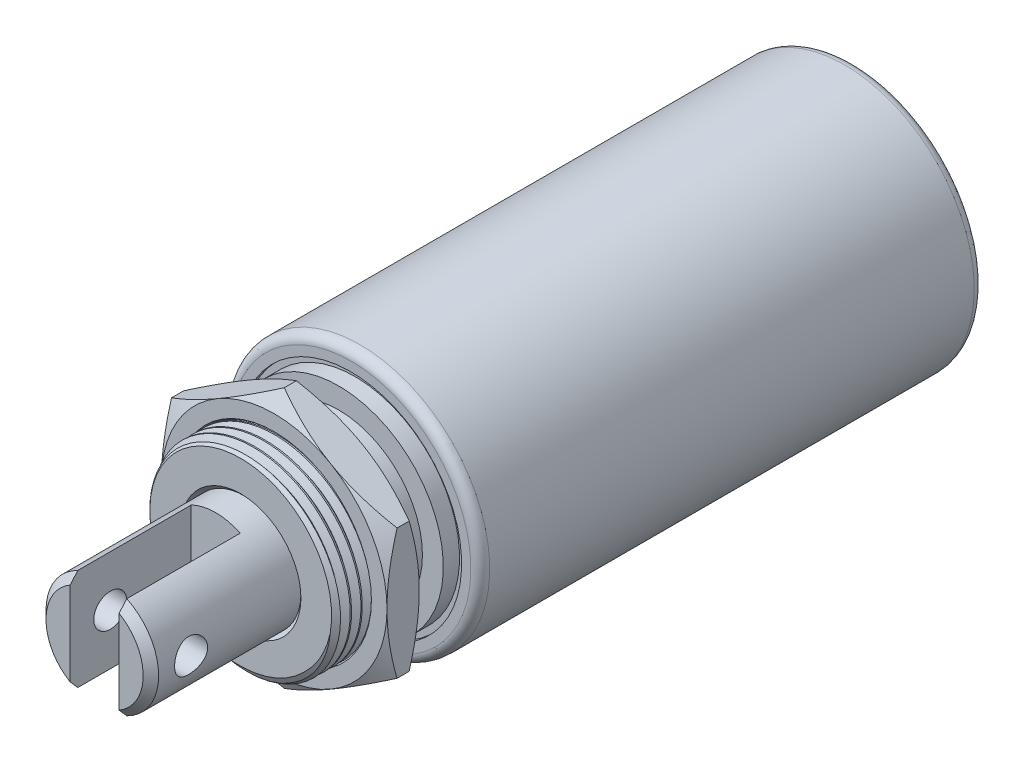
SolidWorks part; units mm, degrees
ref_plane "Front Plane" through (0, 0, 0) normal (0, 0, 1) x (1, 0, 0)
ref_plane "Top Plane" through (0, 0, 0) normal (0, 1, 0) x (1, 0, 0)
ref_plane "Right Plane" through (0, 0, 0) normal (1, 0, 0) x (0, 0, -1)
sketch "Sketch0" plane through (0, 0, 0) normal (1, 0, 0) x (0, 0, -1)
  line L0 (0, 0) -> (51.1556, 0) construction
  line L1 (0, 0) -> (-24.0538, 0) construction
  line L2 (51.1556, 12.7635) -> (51.1556, -12.7635) construction
  line L3 (0, 9.464) -> (0, -9.464) construction
  line L4 (-24.0538, 5.5499) -> (-24.0538, -5.5499) construction
  line L5 (-24.0538, 0) -> (-49.4538, 0) construction
  point P10 (-20.0914, 0)
  point P12 (-9.652, 0)
  dimension "D1" = 20.0914
  dimension "Lg." = 51.1556
  dimension "Dia." = 25.527
  dimension "Rod Dia." = 11.0998
  dimension "A" = 24.0538
  dimension "Thread OD" = 18.9281
  dimension "Stroke" = 25.4
  dimension "D2" = 3.9624
  dimension "D3" = 9.652
sketch "Sketch1" plane through (0, 0, 0) normal (1, 0, 0) x (0, 0, -1)
  line L0 (51.1556, 0) -> (0, 0) construction
  line L1 (49.8729, 12.7635) -> (2.1209, 12.7635)
  line L2 (51.1556, 2.2225) -> (51.1556, 0)
  line L3 (51.1556, 0) -> (0, 0)
  line L4 (1.6002, 10.922) -> (1.6002, 10.3124)
  line L5 (50.8, 2.5781) -> (50.8, 11.8364)
  line L6 (1.1938, 11.8364) -> (1.1938, 10.922)
  line L7 (1.1938, 10.922) -> (1.6002, 10.922)
  line L8 (1.6002, 10.3124) -> (0, 10.3124)
  line L9 (0, 10.3124) -> (0, 0)
  arc A0 (51.1556, 2.2225) -> (50.8, 2.5781) centre (50.8, 2.2225) ccw
  arc A1 (50.8, 11.8364) -> (49.8729, 12.7635) centre (49.8729, 11.8364) ccw
  arc A2 (1.1938, 11.8364) -> (2.1209, 12.7635) centre (2.1209, 11.8364) cw
  dimension "D1" = 0.9271
  dimension "D4" = 1.1938
  dimension "D2" = 0.3556
  dimension "D3" = 4.445
  dimension "D5" = 21.844
  dimension "D6" = 0.4064
  dimension "D7" = 20.6248
revolve "Revolve1" add sketch "Sketch1" angle 360 mid plane about L0
sketch "Sketch2" plane through (0, 0, 0) normal (1, 0, 0) x (0, 0, -1)
  line L0 (0, 0) -> (-24.0538, 0) construction
  line L3 (-9.652, 5.9309) -> (-9.652, 8.956)
  line L4 (-9.652, 8.956) -> (-9.144, 9.464)
  line L5 (-9.144, 9.464) -> (-2.479, 9.464)
  line L6 (-2.479, 9.464) -> (-1.27, 8.255)
  line L7 (-1.27, 8.255) -> (0, 8.255)
  line L8 (0, 8.255) -> (0, 5.5499)
  line L9 (-9.271, 5.5499) -> (0, 5.5499)
  line L11 (-9.271, 5.5499) -> (-9.652, 5.9309)
  dimension "D1" = 1.27
  dimension "D4" = 0.508
  dimension "D5" = 9.652
  dimension "D2" = 45
  dimension "D6" = 1.209
  dimension "D3" = 45
  dimension "D8" = 0.381
  dimension "D7" = 45
revolve "Revolve2" add sketch "Sketch2" angle 360 mid plane about L0
sketch "Sketch3" plane through (0, 0, 0) normal (1, 0, 0) x (0, 0, -1)
  line L0 (-24.0538, 0) -> (0, 0) construction
  line L1 (-23.2918, 5.5499) -> (-24.0538, 4.7879)
  line L2 (0, 0) -> (-24.0538, 0)
  line L3 (0, 0) -> (0, 5.5499)
  line L4 (0, 5.5499) -> (-23.2918, 5.5499)
  line L5 (-24.0538, 0) -> (-24.0538, 4.7879)
  line L6 (-23.2918, 5.5499) -> (-24.0538, 5.5499) construction
  line L7 (-24.0538, 5.5499) -> (-24.0538, 4.7879) construction
  dimension "D1" = 0.762
revolve "Revolve3" add sketch "Sketch3" angle 360 mid plane about L2
sketch "Sketch4" plane through (0, 0, 0) normal (0, 1, 0) x (0, 0, -1)
  line L1 (-24.0538, 2.413) -> (-12.1158, 2.413)
  line L2 (-24.0538, 2.413) -> (-24.0538, -2.413)
  line L3 (-24.0538, -2.413) -> (-12.1158, -2.413)
  line L4 (-12.1158, 2.413) -> (-12.1158, -2.413)
  dimension "D1" = 4.826
  dimension "D2" = 11.938
extrude "Cut-Extrude1" cut sketch "Sketch4" against normal up to surface and the other way up to surface up to face at (0, 5.5499, 23.2918) other way up to face at (0, 5.5499, 23.2918)
sketch "Sketch5" plane through (0, 0, 0) normal (1, 0, 0) x (0, -1, 0)
  line L0 (0, -24.0538) -> (0, -20.0914) construction
  circle A0 centre (0, -20.0914) radius 1.6256
  dimension "D1" = 3.2512
extrude "Cut-Extrude2" cut sketch "Sketch5" along normal up to surface and the other way up to surface up to face at (0, 0, 17.7038) other way up to face at (0, 0, 17.7038)
move or copy body "Body-Move/Copy1" bodies to move or copy 107 copy yes number of copies 1 translate (0, 0, 25.4)
sketch "SketchX" plane through (0, 0, 0) normal (1, 0, 0) x (0, 0, -1)
  line L0 (-48.6918, -4.9979) -> (-37.5158, -4.9979) construction
  line L2 (-48.6918, 4.9979) -> (-37.5158, 4.9979) construction
  line L3 (-49.4538, 4.1354) -> (-49.4538, -4.1354) construction
  line L4 (-49.4538, 4.1354) -> (-49.4538, -4.1354)
  line L7 (-37.5158, 5.5499) -> (-37.5158, 4.9979) construction
  line L8 (-25.4, 5.5499) -> (-37.5158, 5.5499) construction
  line L11 (-37.5158, -4.9979) -> (-37.5158, -5.5499) construction
  line L12 (-37.5158, -5.5499) -> (-25.4, -5.5499) construction
  line L13 (-48.6918, -4.9979) -> (-37.5158, -4.9979)
  line L15 (-48.6918, 4.9979) -> (-37.5158, 4.9979)
  line L16 (-37.5158, 5.5499) -> (-37.5158, 4.9979)
  line L17 (-12.1158, 5.5499) -> (-37.5158, 5.5499)
  line L18 (-37.5158, -4.9979) -> (-37.5158, -5.5499)
  line L19 (-37.5158, -5.5499) -> (-12.1158, -5.5499)
  circle A2 centre (-45.4914, 0) radius 1.6256 construction
  circle A5 centre (-45.4914, 0) radius 1.6256
  spline S0 degree 3 poles (-1434.4786, -1445.2829) (1443.8208, 1319.7519) (-1538.9887, -1332.4105) (1339.788, 1433.0653) knots -101.772608 -101.772608 -101.772608 -101.772608 98.765964 98.765964 98.765964 98.765964 only from (-48.6918, -4.9979) to (-49.4538, -4.1354) construction
  spline S1 degree 3 poles (1394.5661, -1377.9374) (-1596.4208, 1274.6807) (1503.9715, -1259.3485) (-1497.3844, 1382.1644) knots -97.820644 -97.820644 -97.820644 -97.820644 102.837817 102.837817 102.837817 102.837817 only from (-49.4538, 4.1354) to (-48.6918, 4.9979) construction
  spline S2 degree 3 poles (-48.6918, -4.9979) (-48.9485, -4.7129) (-49.203, -4.4258) (-49.4538, -4.1354) knots 0 0 0 0 1 1 1 1
  spline S3 degree 3 poles (-49.4538, 4.1354) (-49.203, 4.4258) (-48.9485, 4.7129) (-48.6918, 4.9979) knots 0 0 0 0 1 1 1 1
delete or keep bodies "Body-Delete1" type delete bodies bodies 108
sketch "Sketch10" plane through (0, 0, 0) normal (0, 0, 1) x (1, 0, 0)
  line L0 (0, 9.464) -> (0, 11.1125) construction
  line L1 (0, 12.8316) -> (-11.1125, 6.4158)
  line L2 (-11.1125, 6.4158) -> (-11.1125, -6.4158)
  line L3 (-11.1125, -6.4158) -> (0, -12.8316)
  line L4 (0, -12.8316) -> (11.1125, -6.4158)
  line L5 (11.1125, -6.4158) -> (11.1125, 6.4158)
  line L6 (11.1125, 6.4158) -> (0, 12.8316)
  circle A0 centre (0, 0) radius 9.464
  circle A1 centre (0, 0) radius 11.1125 construction
  dimension "D1" = 22.225
extrude "Boss-Extrude3" add sketch "Sketch10" along normal blind 3.175 from offset 3.175 separate body
sketch "Sketch11" plane through (0, 0, 0) normal (1, 0, 0) x (0, 0, -1)
  line L0 (-6.35, 0) -> (-3.175, 0) construction
  line L1 (-6.35, 12.8316) -> (-6.35, 11.1125)
  line L2 (-6.35, 6.4158) -> (-6.35, 12.8316) construction
  line L3 (-6.35, 11.1125) -> (-5.3575, 12.8316)
  line L4 (-6.35, 12.8316) -> (-3.175, 12.8316) construction
  line L5 (-5.3575, 12.8316) -> (-6.35, 12.8316)
  line L6 (-3.175, 12.8316) -> (-3.175, 11.1125)
  line L7 (-3.175, 6.4158) -> (-3.175, 12.8316) construction
  line L8 (-3.175, 11.1125) -> (-4.1675, 12.8316)
  line L9 (-4.1675, 12.8316) -> (-3.175, 12.8316)
  line L10 (-6.35, 11.1125) -> (0, 11.1125) construction
  line L11 (-6.35, 9.5786) -> (-6.35, 9.464)
  line L12 (-6.35, 9.464) -> (-6.2354, 9.464)
  line L13 (-6.2354, 9.464) -> (-6.35, 9.5786)
  line L14 (-3.175, 9.5786) -> (-3.175, 9.464)
  line L15 (-3.175, 9.464) -> (-3.2896, 9.464)
  line L16 (-3.2896, 9.464) -> (-3.175, 9.5786)
  line L20 (-6.35, 9.464) -> (-6.35, -9.464) construction
  line L21 (-3.175, -9.464) -> (-3.175, 9.464) construction
  dimension "D1" = 30
  dimension "D2" = 0.1146
revolve "Cut-Revolve1" cut sketch "Sketch11" angle 360 about L0
sketch "Sketch6" plane through (0, 0, 9.652) normal (0, 0, 1) x (1, 0, 0)
  circle A1 centre (0, 0) radius 9.464
  point P1 (0, 9.464)
curve "Helix/Spiral1" pitch 1.0583 height 9.4403 radius 9.464 centre (0, 0, 9.652) axis (0, 0, -1) start towards (0, 1, 0) parameters "Pitch"=1.0583
sketch "Sketch7" plane through (0, 0, 0) normal (1, 0, 0) x (0, 0, -1)
  line L0 (-10.6442, 9.5786) -> (-9.5859, 9.5786) construction
  line L1 (-9.5859, 9.5786) -> (-10.115, 8.6621) construction
  line L2 (-10.115, 8.6621) -> (-10.6442, 9.5786) construction
  line L3 (-10.1812, 8.7766) -> (-10.0489, 8.7766) construction
  line L4 (-10.578, 9.464) -> (-9.652, 9.464) construction
  line L5 (-10.115, 8.6621) -> (-10.115, 8.7766) construction
  line L6 (-10.115, 9.464) -> (-10.115, 9.5786) construction
  line L7 (-10.1812, 8.7766) -> (-10.0489, 8.7766)
  line L8 (-10.0489, 8.7766) -> (-9.6189, 9.5213)
  line L9 (-9.6189, 9.5213) -> (-10.6111, 9.5213)
  line L10 (-10.6111, 9.5213) -> (-10.1812, 8.7766)
  line L11 (-10.115, 8.6621) -> (-10.115, -9.464) construction
  line L12 (-10.115, -9.464) -> (-9.0567, -9.464) construction
  line L13 (-9.0567, -9.464) -> (-7.9984, -9.464) construction
  line L14 (-7.9984, -9.464) -> (-6.94, -9.464) construction
  line L15 (-9.144, -9.464) -> (-2.479, -9.464) construction
  point P15 (-10.115, 9.5213)
  dimension "D1" = 1.0583
  dimension "D2" = 0.1323
sweep "Cut-Sweep1" cut profiles "Sketch7" path "Helix/Spiral1"
equation "\"D3@Helix/Spiral1\" = \"Pitch@Helix/Spiral1\" + \"D5@Sketch2\" - \"D1@Sketch2\""
equation "\"D1@Sketch7\" = \"Pitch@Helix/Spiral1\""
equation "\"D2@Sketch7\" = \"D1@Sketch7\" / 8"
